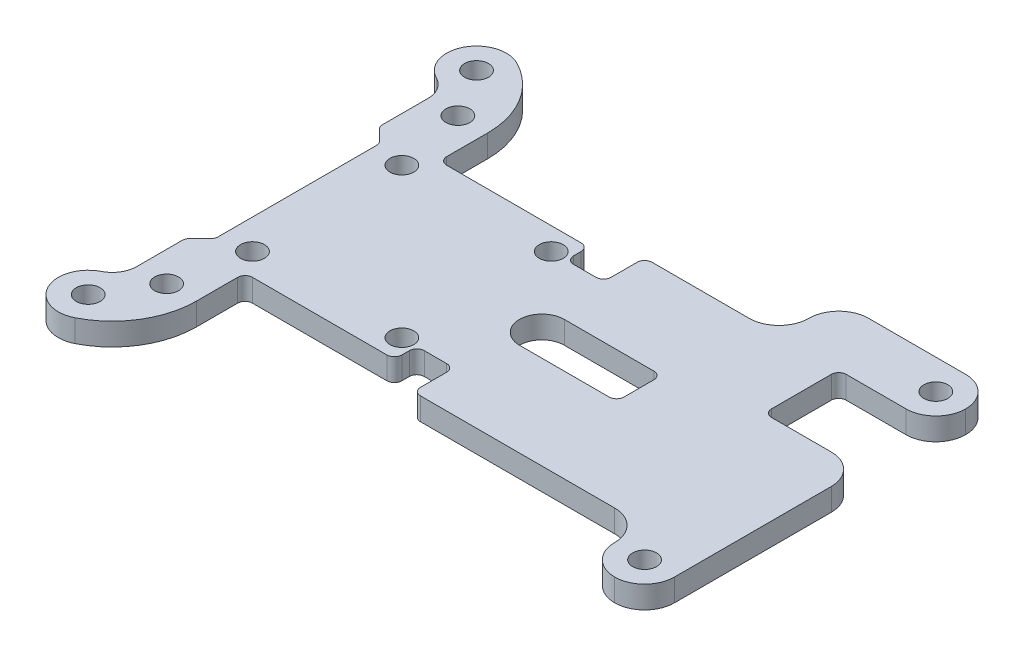
SolidWorks part; units mm, degrees
material "Caucho"
ref_plane "Alzado" through (0, 0, 0) normal (0, 0, 1) x (1, 0, 0)
ref_plane "Planta" through (0, 0, 0) normal (0, 1, 0) x (1, 0, 0)
ref_plane "Vista lateral" through (0, 0, 0) normal (1, 0, 0) x (0, 0, -1)
sketch "Croquis1" plane through (0, 0, 0) normal (0, 1, 0) x (1, 0, 0)
  line L1 (-36, -23.5) -> (36, -23.5)
  line L2 (-36, -23.5) -> (-36, 23.5)
  line L3 (-36, 23.5) -> (36, 23.5)
  line L4 (36, -23.5) -> (36, 23.5)
  line L5 (-36, -23.5) -> (36, 23.5) construction
  line L6 (-36, 23.5) -> (36, -23.5) construction
  point P0 (0, 0)
  dimension "D1" = 72
  dimension "D2" = 47
extrude "Saliente-Extruir1" add sketch "Croquis1" along normal blind 3
sketch "Croquis3" plane through (0, 3, 0) normal (0, 1, 0) x (1, 0, 0)
  line L0 (-8, 13) -> (-8, 10)
  line L1 (-36, 23.5) -> (15, 23.5)
  line L2 (-28, 19.5) -> (-28, 13)
  line L3 (-28, 13) -> (-8, 13)
  line L5 (-28, -13) -> (-8, -13)
  line L6 (-28, -13) -> (-28, -19.5)
  line L7 (-36, -23.5) -> (28, -23.5)
  line L9 (36, 23.5) -> (-36, 23.5) construction
  line L19 (-36, 23.5) -> (-36, -23.5) construction
  line L20 (-36, -23.5) -> (36, -23.5) construction
  line L21 (15, 15.5) -> (15, 23.5)
  line L22 (-8, 10) -> (-3, 10)
  line L29 (-8, -13) -> (-8, -10)
  line L37 (36, -23.5) -> (36, 23.5) construction
  line L38 (36, 15.5) -> (23, 15.5)
  line L39 (36, 15.5) -> (36, 5.5)
  line L40 (36, 5.5) -> (23, 5.5)
  line L41 (23, 15.5) -> (23, 5.5)
  line L43 (-3, -15.5) -> (28, -15.5)
  line L45 (28, -15.5) -> (28, -23.5)
  line L46 (-3, 10) -> (-3, 15.5)
  line L47 (-3, 15.5) -> (15, 15.5)
  line L51 (-8, -10) -> (-3, -10)
  line L52 (-3, -10) -> (-3, -15.5)
  line L54 (-36, 23.5) -> (-36, -23.5) construction
  line L55 (-36, 10.5) -> (-34, 10.5)
  line L56 (-36, 10.5) -> (-36, -10.5)
  line L57 (-36, -10.5) -> (-34, -10.5)
  line L58 (-34, 10.5) -> (-34, -10.5)
  line L59 (-36, 23.5) -> (-36, 10.5) construction
  line L60 (-36, -10.5) -> (-36, -23.5) construction
  line L61 (-28, -19.5) -> (-36, -19.5)
  line L62 (-36, -19.5) -> (-36, -23.5)
  line L65 (-36, 23.5) -> (-36, 19.5)
  line L66 (-36, 19.5) -> (-28, 19.5)
  point P12 (0, 0)
  dimension "D1" = 26
  dimension "D2" = 8
  dimension "D3" = 8
  dimension "D4" = 3
  dimension "D5" = 20
  dimension "D6" = 13
  dimension "D7" = 8
  dimension "D8" = 8
  dimension "D9" = 8
  dimension "D10" = 10
  dimension "D11" = 5
  dimension "D12" = 13
  dimension "D13" = 2
  dimension "D14" = 4
extrude "Cortar-Extruir2" cut sketch "Croquis3" against normal through all
sketch "Croquis2" plane through (0, 3, 0) normal (0, 1, 0) x (1, 0, 0)
  line L1 (-32, -19.5) -> (32, -19.5) construction
  line L3 (-32, 19.5) -> (32, 19.5) construction
  line L4 (32, -19.5) -> (32, 19.5) construction
  line L5 (-32, -19.5) -> (32, 19.5) construction
  line L6 (-32, 19.5) -> (32, -19.5) construction
  line L8 (-32, 19.5) -> (-32, -19.5) construction
  circle A4 centre (-32, 19.5) radius 1.6
  circle A5 centre (32, 19.5) radius 1.6
  circle A6 centre (32, -19.5) radius 1.6
  circle A7 centre (-32, -19.5) radius 1.6
  point P0 (0, 0)
  dimension "D1" = 3.2
  dimension "D2" = 39
  dimension "D3" = 64
extrude "Cortar-Extruir1" cut sketch "Croquis2" against normal through all
sketch "Croquis5" plane through (0, 3, -3) normal (0, -1, 0) x (1, 0, 0)
  line L0 (-30, 13) -> (-30, -7) construction
  line L7 (0, 3) -> (-30, 3) construction
  line L10 (-30, 13) -> (-10, 13) construction
  line L11 (-30, -7) -> (-10, -7) construction
  line L12 (-10, 13) -> (-10, -7) construction
  circle A8 centre (-30, 13) radius 1.6
  circle A9 centre (-30, -7) radius 1.6
  circle A10 centre (-10, 13) radius 1.6
  circle A11 centre (-10, -7) radius 1.6
  point P0 (0, 3)
  dimension "D1" = 3.2
  dimension "D4" = 20
  dimension "D6" = 30
sketch "Croquis4" plane through (0, 3, 0) normal (0, 1, 0) x (1, 0, 0)
  line L0 (36, -23.5) -> (36, 5.5) construction
  line L1 (0, 0) -> (-1.25, 0) construction
  line L3 (-1.25, -3) -> (11.75, -3)
  line L4 (-1.25, -3) -> (-1.25, 3) construction
  line L5 (-1.25, 3) -> (11.75, 3)
  line L6 (11.75, -3) -> (11.75, 3)
  line L7 (-1.25, -3) -> (11.75, 3) construction
  line L8 (-1.25, 3) -> (11.75, -3) construction
  arc A0 (-1.25, 3) -> (-1.25, -3) centre (-1.25, 0) ccw
  point P5 (5.25, 0)
  point P11 (-1.25, 0)
  dimension "D1" = 6
  dimension "D2" = 24.25
  dimension "D4" = 13
extrude "Cortar-Extruir3" cut sketch "Croquis4" against normal blind 34.75
extrude "Cortar-Extruir7" cut sketch "Croquis5" along normal blind 10
fillet "Chaflán1" radius 2.5 2 edges at (-36, 1.5, 10.5) (-36, 1.5, -10.5) profile chamfer
fillet "Redondeo2" radius 1 18 edges at (-8, 1.5, 13) (-8, 1.5, -13) (-28, 1.5, -13) (-28, 1.5, 13) (23, 1.5, -5.5) (23, 1.5, -15.5) (11.75, 1.5, 3) (11.75, 1.5, -3) (-3, 1.5, -15.5) (-3, 1.5, -10) (-8, 1.5, -10) (-3, 1.5, 15.5) (-3, 1.5, 10) (-8, 1.5, 10) (-34, 1.5, 11) (-36, 1.5, 13) (-34, 1.5, -11) (-36, 1.5, -13)
sketch "Croquis6" plane through (0, 3, 0) normal (0, 1, 0) x (1, 0, 0)
  line L1 (-32, -19.5) -> (-32, -26) construction
  line L2 (-32, -26) -> (-36, -26) construction
  circle A4 centre (-36, -26) radius 1.6
  arc A6 (-32, -19.5) -> (-36, -26) centre (-39.2813, -19.5) cw construction
  arc A7 (-34.1974, -29.5708) -> (-28, -19.5) centre (-39.2813, -19.5) ccw
  arc A8 (-37.8026, -22.4292) -> (-36, -19.5) centre (-39.2813, -19.5) ccw
  arc A9 (-37.8026, -22.4292) -> (-34.1974, -29.5708) centre (-36, -26) ccw
  arc A10 (-28, -19.5) -> (-36, -19.5) centre (-32, -19.5) ccw
  circle A11 centre (-32, -19.5) radius 1.6 construction
  circle A12 centre (-32, -19.5) radius 1.6
  point P5 (-33.0801, -23.3161)
  dimension "D3" = 4
  dimension "D1" = 3.2
  dimension "D4" = 4
  dimension "D2" = 6.5
extrude "Saliente-Extruir2" add sketch "Croquis6" against normal through all contours A9 A4 region at (-33.6017, 3, 22.9951)
mirror "Simetría1" about plane through (0, 0, 0) normal (0, 0, 1) of "Saliente-Extruir2"
fillet "Redondeo1" radius 4 8 edges at (36, 1.5, -23.5) (36, 1.5, 23.5) (15, 1.5, -23.5) (15, 1.5, -15.5) (28, 1.5, 15.5) (36, 1.5, -5.5) (36, 1.5, -15.5) (28, 1.5, 23.5)
